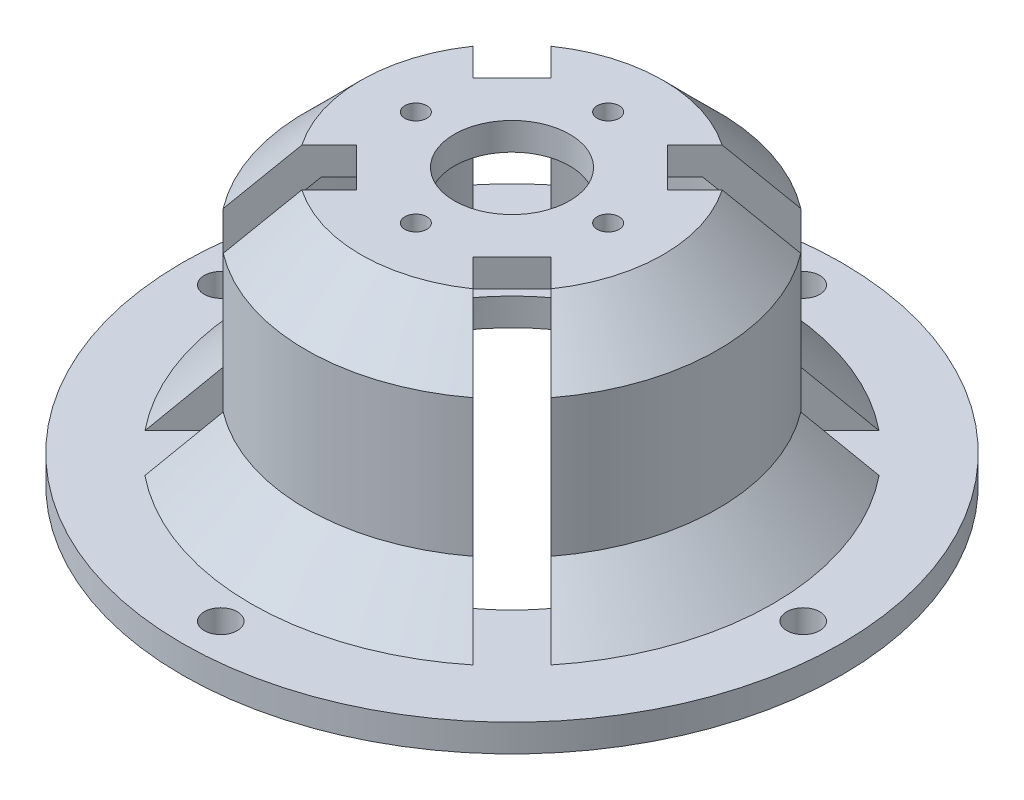
SolidWorks part; units mm, degrees
ref_plane "Front Plane" through (0, 0, 0) normal (0, 0, 1) x (1, 0, 0)
ref_plane "Top Plane" through (0, 0, 0) normal (0, 1, 0) x (1, 0, 0)
ref_plane "Right Plane" through (0, 0, 0) normal (1, 0, 0) x (0, 0, -1)
ref_axis "CentreAxist" through (0, 45.9861, 0) along (0, -1, 0)
sketch "Sketch1" plane through (0, 0, 0) normal (0, 1, 0) x (1, 0, 0)
  circle A1 centre (0, 0) radius 60
  dimension "D2" = 120
extrude "Stock" add sketch "Sketch1" against normal blind 50
sketch "Sketch7" plane through (0, 0, 0) normal (0, 1, 0) x (1, 0, 0)
  circle A0 centre (0, 0) radius 10.5
  dimension "D1" = 21
sketch "Sketch8" plane through (0, 0, 0) normal (0, 1, 0) x (1, 0, 0)
  circle A0 centre (0, 0) radius 35
  dimension "D1" = 70
extrude "HollowInterior" cut sketch "Sketch8" against normal up to next from offset 5 offset against normal yes
extrude "HoleForMotorShaft" cut sketch "Sketch7" against normal through all
sketch "Sketch9" plane through (0, 0, 0) normal (0, 1, 0) x (1, 0, 0)
  circle A0 centre (0, 0) radius 37.5
  dimension "D1" = 75
extrude "ExteriorLathe" cut sketch "Sketch9" along direction (0, 1, 0) on the side against the normal offset from surface (45 mm away) 5 from surface flip side to cut up to face at (0, -50, 35) starting at face at (0, 0, 10.5)
chamfer "Chamfer1" distance 10 angle 45 1 edges at (0, -5, 35)
chamfer "Chamfer2" distance 10 angle 45 1 edges at (0, 0, 37.5)
chamfer "Chamfer3" distance 10 angle 45 1 edges at (0, -45, 37.5)
sketch "Sketch10" plane through (0, 0, 0) normal (0, 1, 0) x (1, 0, 0)
  line L0 (-14.1421, 14.1421) -> (-33.5876, 33.5876)
  line L1 (0, 0) -> (0, 47.5) construction
  line L2 (-14.1421, 14.1421) -> (0, 0) construction
  line L3 (14.1421, 14.1421) -> (0, 0) construction
  line L4 (14.1421, 14.1421) -> (33.5876, 33.5876)
  line L5 (14.1421, -14.1421) -> (0, 0) construction
  line L6 (14.1421, -14.1421) -> (33.5876, -33.5876)
  line L7 (-14.1421, -14.1421) -> (0, 0) construction
  line L8 (-14.1421, -14.1421) -> (-33.5876, -33.5876)
  circle A1 centre (0, 0) radius 47.5 construction
  point P9 (0, 0)
  point P16 (0, 0)
  dimension "D2" = 4
  dimension "D1" = 95
  dimension "D3" = 45
extrude "SlotsForFun" cut sketch "Sketch10" against normal up to surface (45 mm away) thin up to face at (0, -45, 47.5) thin type mid plane wall 10
sketch "Sketch13" plane through (0, 0, 0) normal (0, 1, 0) x (1, 0, 0)
  line L0 (0, 0) -> (0, 17.5) construction
  line L1 (0, 0) -> (17.5, 0) construction
  line L2 (0, 0) -> (0, -17.5) construction
  line L3 (0, 0) -> (-17.5, 0) construction
  circle A0 centre (0, 17.5) radius 2
  circle A1 centre (17.5, 0) radius 2
  circle A2 centre (0, -17.5) radius 2
  circle A3 centre (-17.5, 0) radius 2
  point P13 (0, 0)
  dimension "D1" = 4
  dimension "D2" = 17.5
  dimension "D3" = 4
extrude "GearboxMountingHoles" cut sketch "Sketch13" against normal up to surface (5 mm away) from surface up to face at (0, -5, 10.5) starting at face at (0, 0, 10.5)
sketch "Sketch14" plane through (0, 0, 0) normal (0, 1, 0) x (1, 0, 0)
  line L0 (0, 0) -> (0, 53) construction
  line L1 (0, 0) -> (53, 0) construction
  line L2 (0, 0) -> (0, -53) construction
  line L3 (0, 0) -> (-53, 0) construction
  circle A0 centre (0, 53) radius 3
  circle A1 centre (53, 0) radius 3
  circle A2 centre (0, -53) radius 3
  circle A3 centre (-53, 0) radius 3
  point P12 (0, 0)
  dimension "D1" = 6
  dimension "D2" = 53
  dimension "D3" = 4
extrude "Cut-Extrude5" cut sketch "Sketch14" against normal up to surface (50 mm away) from surface up to face at (0, -50, 35) starting at face at (0, -45, 0)
